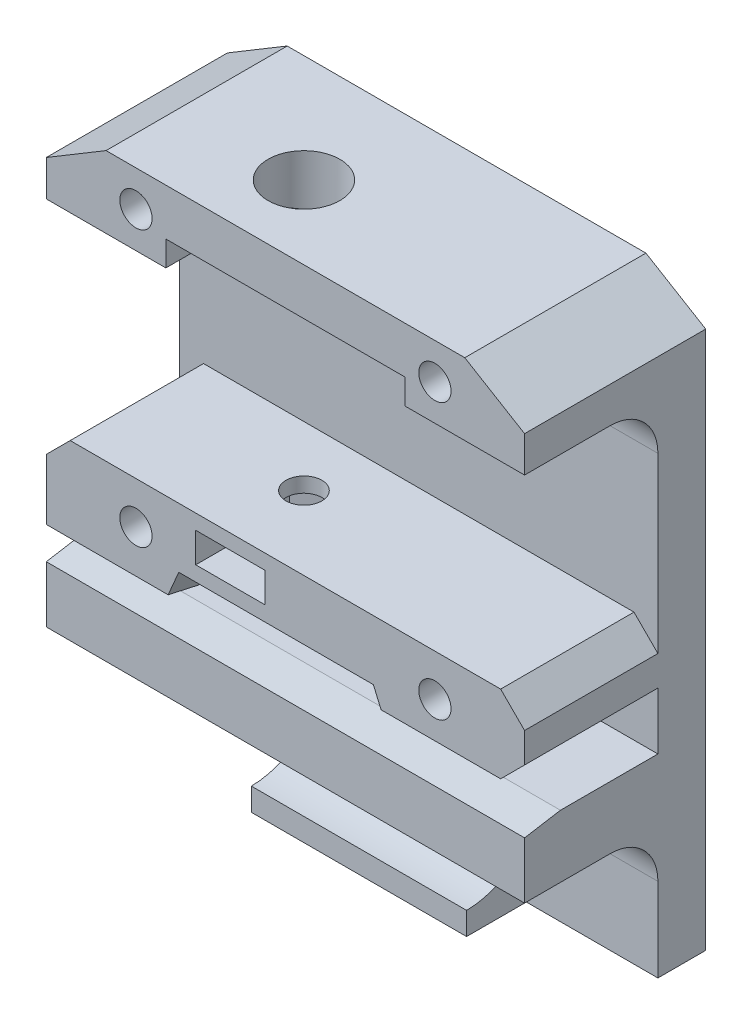
SolidWorks part; units mm, degrees
material "ABS"
ref_plane "Front Plane" through (0, 0, 0) normal (0, 0, 1) x (1, 0, 0)
ref_plane "Top Plane" through (0, 0, 0) normal (0, 1, 0) x (1, 0, 0)
ref_plane "Right Plane" through (0, 0, 0) normal (1, 0, 0) x (0, 0, -1)
sketch "Sketch1" plane through (0, 0, 0) normal (0, 0, 1) x (1, 0, 0)
  line L1 (-23.7591, 22) -> (52.715, 22) construction
  line L2 (0, -10) -> (0, 38)
  line L3 (0, 38) -> (40, 38)
  line L4 (40, -10) -> (40, 38)
  line L6 (0, -10) -> (40, -10)
  point P2 (0, 22)
  point P9 (40, 22)
  point P10 (0, 22)
  point P13 (40, 22)
  dimension "D1" = 48
  dimension "D2" = 40
extrude "Boss-Extrude1" add sketch "Sketch1" along normal blind 4
ref_plane "Plane2" through (0, 13, 0) normal (0, -1, 0) x (1, 0, 0)
sketch "Sketch2" plane through (0, 0, 4) normal (0, 0, 1) x (1, 0, 0)
  line L0 (20, 38) -> (20, 20.7808) construction
  line L1 (15.9, 33) -> (24.1, 33)
  line L2 (15.9, 33) -> (15.9, 23)
  line L3 (15.9, 23) -> (24.1, 23)
  line L4 (24.1, 33) -> (24.1, 23)
  line L5 (40, 38) -> (0, 38) construction
  line L6 (-2.2, 13) -> (2.2, 13) construction
  line L9 (2, 3) -> (10.2, 3)
  line L10 (2, 3) -> (2, -7)
  line L11 (2, -7) -> (10.2, -7)
  line L12 (10.2, 3) -> (10.2, -7)
  line L14 (29.8, 3) -> (29.8, -7)
  line L15 (38, -7) -> (29.8, -7)
  line L16 (38, 3) -> (38, -7)
  line L17 (38, 3) -> (29.8, 3)
  line L18 (15.9, 28) -> (24.1, 28) construction
  line L19 (2, -2) -> (38, -2) construction
  dimension "D1" = 8.2
  dimension "D2" = 10
  dimension "D3" = 20
  dimension "D4" = 4.1
  dimension "D5" = 30
  dimension "D6" = 2
extrude "Cut-Extrude1" [suppressed] cut sketch "Sketch2" against normal blind 1
sketch "Sketch3" [suppressed] plane through (0, 0, 3) normal (0, 0, 1) x (1, 0, 0)
  line L0 (15.9, 33) -> (15.9, 23) construction
  line L1 (15.9, 32.1) -> (24.1, 32.1)
  line L2 (15.9, 32.1) -> (15.9, 23.9)
  line L3 (15.9, 23.9) -> (24.1, 23.9)
  line L4 (24.1, 32.1) -> (24.1, 23.9)
  line L5 (24.1, 23) -> (24.1, 33) construction
  line L6 (24.1, 33) -> (15.9, 33) construction
  line L7 (15.9, 23) -> (24.1, 23) construction
  line L8 (2, 3) -> (2, -7) construction
  line L9 (2, 2.1) -> (10.2, 2.1)
  line L10 (2, 2.1) -> (2, -6.1)
  line L11 (2, -6.1) -> (10.2, -6.1)
  line L12 (10.2, 2.1) -> (10.2, -6.1)
  line L13 (10.2, -7) -> (10.2, 3) construction
  line L14 (29.8, 3) -> (29.8, -7) construction
  line L15 (29.8, 2.1) -> (38, 2.1)
  line L16 (29.8, 2.1) -> (29.8, -6.1)
  line L17 (29.8, -6.1) -> (38, -6.1)
  line L18 (38, 2.1) -> (38, -6.1)
  line L19 (38, -7) -> (38, 3) construction
  line L20 (2, -7) -> (10.2, -7) construction
  dimension "D1" = 0.9
  dimension "D2" = 0.9
  dimension "D3" = 0.9
extrude "Cut-Extrude2" [suppressed] cut sketch "Sketch3" against normal blind 4
chamfer "Chamfer1" [suppressed] distance 1 angle 45
sketch "Sketch4" [suppressed] plane through (0, 0, 3) normal (0, 0, 1) x (1, 0, 0)
  line L0 (24.1, 35.1) -> (15.9, 35.1) construction
  line L1 (15.9, 35.1) -> (15.9, 26.9) construction
  line L2 (2, 1) -> (38, 1) construction
  line L3 (2, 5.1) -> (2, -3.1) construction
  line L4 (38, -7) -> (38, 3) construction
  line L5 (6.1, 2.1) -> (6.1, -3.1) construction
  line L7 (2, -3.1) -> (10.2, -3.1) construction
  line L8 (33.9, 2.1) -> (33.9, -3.1) construction
  line L10 (29.8, -3.1) -> (38, -3.1) construction
  line L12 (10.2, 2.1) -> (2, 2.1) construction
  line L13 (38, 2.1) -> (29.8, 2.1) construction
  circle A0 centre (20, 31) radius 1.65
  circle A1 centre (6.1, 1) radius 1.65
  circle A2 centre (33.9, 1) radius 1.65
  dimension "D1" = 3.3
  dimension "D2" = 4.1
  dimension "D3" = 4.1
extrude "Cut-Extrude3" [suppressed] cut sketch "Sketch4" against normal through all
ref_plane "Plane1" through (20, 0, 0) normal (1, 0, 0) x (0, 0, -1)
sketch "Sketch5" plane through (0, 0, 4) normal (0, 0, 1) x (1, 0, 0)
  line L0 (-5.9966, 13) -> (42.103, 13) construction
  line L1 (0.9, 8.125) -> (0, 8.125)
  line L2 (40, 6.225) -> (40, 1)
  line L3 (0, 6.225) -> (40, 6.225)
  line L4 (40, 15.5) -> (40, 9)
  line L5 (40, 9) -> (28, 9)
  line L6 (20, -2.2) -> (20, 2.2) construction
  line L7 (0, -10) -> (40, -10) construction
  line L8 (0, 1) -> (40, 1)
  line L9 (27.3571, 10.5) -> (11.0812, 10.5)
  line L10 (28, 9) -> (27.3571, 10.5)
  line L11 (5.9219, 8.125) -> (6.2219, 7.425)
  line L12 (11.0812, 10.5) -> (9.7634, 7.425)
  line L13 (6.2219, 7.425) -> (7.2317, 7.425)
  line L14 (-2.2, 13) -> (2.2, 13) construction
  line L15 (7.2317, 7.425) -> (7.5317, 8.125)
  line L16 (8.5004, 8.125) -> (8.8004, 7.425)
  line L17 (8.8004, 7.425) -> (9.7634, 7.425)
  line L18 (5.9219, 8.125) -> (5, 8.125)
  line L23 (1.2, 7.425) -> (0.9, 8.125)
  line L27 (2.5, 8.125) -> (2.2, 7.425)
  line L28 (2.2, 7.425) -> (1.2, 7.425)
  line L29 (11, -10) -> (29, -10)
  line L30 (3.7, 7.425) -> (3.4, 8.125)
  line L31 (3.4, 8.125) -> (2.5, 8.125)
  line L32 (5, 8.125) -> (4.7, 7.425)
  line L33 (4.7, 7.425) -> (3.7, 7.425)
  line L34 (11, -10) -> (11, -5)
  line L36 (8.5004, 8.125) -> (7.5317, 8.125)
  line L40 (40, -10) -> (40, 38) construction
  line L42 (40, 15.5) -> (0, 15.5)
  line L43 (0, 15.5) -> (0, 8.125)
  line L46 (0, 38) -> (0, -10) construction
  line L47 (0, 32) -> (40, 32)
  line L48 (0, 32) -> (0, 38)
  line L49 (11, -5) -> (29, -5)
  line L50 (40, 32) -> (40, 38)
  line L51 (0, 38) -> (40, 38)
  line L52 (29, -10) -> (29, -5)
  line L53 (40, 38) -> (0, 38) construction
  line L62 (0, 6.225) -> (0, 1)
  point P84 (20, 6.225)
  dimension "D2" = 0.7
  dimension "D3" = 0.9
  dimension "D4" = 0.3
  dimension "D5" = 0.3
  dimension "D7" = 1
  dimension "D9" = 5
  dimension "D10" = 4
  dimension "D11" = 1.9
  dimension "D14" = 18
  dimension "D15" = 5
  dimension "D19" = 2.5
  dimension "D8" = 4.875
  dimension "D12" = 12
  dimension "D13" = 12
  dimension "D6" = 19
extrude "Boss-Extrude2" add sketch "Sketch5" along normal blind 11.15 and the other way up to surface (4 mm away) other way up to face at (20, 14, 0)
fillet "Fillet1" radius 4 2 edges at (20, 32, 4) (20, 1, 4) tangent propagation no
sketch "Sketch6" plane through (0, 0, 15.15) normal (0, 0, 1) x (1, 0, 0)
  line L0 (7.5, 41.1026) -> (7.5, 12.7734) construction
  line L2 (20, 38) -> (20, 13.7163) construction
  line L3 (20, -2.2) -> (20, 2.2) construction
  line L4 (-2.2, 13) -> (2.2, 13) construction
  line L6 (40, 38) -> (0, 38) construction
  circle A0 centre (7.5, 35) radius 1.35
  circle A1 centre (7.5, 12) radius 1.35
  circle A2 centre (32.5, 35) radius 1.35
  circle A3 centre (32.5, 12) radius 1.35
  dimension "D1" = 2.7
  dimension "D2" = 23
  dimension "D3" = 22
  dimension "D4" = 12.5
extrude "Cut-Extrude4" cut sketch "Sketch6" against normal through all
chamfer "Chamfer2" distance 2 angle 45 3 edges at (0, 15.5, 9.575) (40, 9, 9.575) (40, 15.5, 9.575)
sketch "Sketch7" plane through (0, 0, 4) normal (0, 0, 1) x (1, 0, 0)
  line L0 (0, 28) -> (0, 13.5) construction
  line L1 (0, 22) -> (40, 22)
  line L2 (0, 22) -> (0, 15.5)
  line L3 (0, 15.5) -> (40, 15.5)
  line L4 (40, 22) -> (40, 15.5)
  line L7 (38, 15.5) -> (2, 15.5) construction
  line L8 (-2.2, 13) -> (2.2, 13) construction
  dimension "D1" = 9
extrude "Cut-Extrude5" [suppressed] cut sketch "Sketch7" against normal blind 3
fillet "Fillet2" [suppressed] radius 3
chamfer "Chamfer3" distance 3 distance2 1 2 edges at (1.7, 7.425, 15.15) (4.2, 7.425, 15.15) first distance on face at (1.7, 7.425, 9.575) first distance on face at (4.2, 7.425, 9.575)
chamfer "Chamfer4" distance 3 distance2 0.5 1 edges at (20, 6.225, 15.15) first distance on face at (20, 6.225, 9.575)
sketch "Sketch8" plane through (20, 0, 0) normal (1, 0, 0) x (0, 0, -1)
  line L0 (-9, 28) -> (-9, -2) construction
  line L1 (-15.15, 38) -> (0, 38) construction
  line L2 (-4, 6.225) -> (-4, 11) construction
  line L4 (-9, 34.1) -> (-18.8209, 34.1)
  line L5 (-18.8209, 34.1) -> (-18.8209, 21.9)
  line L6 (-18.8209, 21.9) -> (-9, 21.9)
  line L8 (-18.8209, -10.4726) -> (-18.8209, -3.1942)
  line L9 (-18.8209, -3.1942) -> (-13.3134, 2.3134)
  line L10 (-9, -8.1) -> (-9, -10.4726)
  line L11 (-9, -10.4726) -> (-18.8209, -10.4726)
  arc A0 (-9, 21.9) -> (-9, 34.1) centre (-9, 28) ccw
  arc A1 (-9, -8.1) -> (-13.3134, 2.3134) centre (-9, -2) ccw
  dimension "D2" = 12.2
  dimension "D1" = 30
  dimension "D3" = 10
  dimension "D4" = 5
  dimension "D5" = 45
extrude "Cut-Extrude6" cut sketch "Sketch8" against normal blind 10 and the other way blind 10
sketch "Sketch12" plane through (0, 38, 0) normal (0, 1, 0) x (1, 0, 0)
  line L1 (10, -4) -> (0, -4) construction
  circle A0 centre (15.4, -9) radius 3
  dimension "D3" = 6
  dimension "D1" = 5
  dimension "D2" = 15.4
extrude "Cut-Extrude8" cut sketch "Sketch12" against normal up to surface (22.5 mm away) up to face at (20, 15.5, 9.575)
sketch "Sketch13" plane through (0, 15.5, 0) normal (0, 1, 0) x (1, 0, 0)
  circle A0 centre (15.4, -9) radius 1.5
  circle A1 centre (15.4, -9) radius 3 construction
  dimension "D1" = 3
extrude "Cut-Extrude10" cut sketch "Sketch13" against normal offset from surface (10.275 mm away) 1 up to face at (20, 6.225, 8.075) offset beyond the face yes
sketch "Sketch9" plane through (0, 13, 0) normal (0, -1, 0) x (1, 0, 0)
  line L0 (12.5, 16.8153) -> (18.3, 16.8153)
  line L1 (15.4, 5.6514) -> (18.3, 7.3257)
  line L2 (18.3, 7.3257) -> (18.3, 16.8153)
  line L5 (12.5, 16.8153) -> (12.5, 7.3257)
  line L6 (12.5, 7.3257) -> (15.4, 5.6514)
  line L8 (13.9872, 11.5329) -> (12.1308, 10.4612) [skipped]
  line L9 (16.8128, 11.5329) -> (14.9564, 12.6047) [skipped]
  circle A0 centre (15.4, 9) radius 2.9 construction
  arc A1 (18.4, 9) -> (12.4, 9) centre (15.4, 9) ccw construction
  dimension "D1" = 5.8
extrude "Cut-Extrude7" cut sketch "Sketch9" against normal blind 1.25 and the other way blind 1.25
chamfer "Chamfer5" distance 5 distance2 3 1 edges at (0, 38, 7.575) first distance on face at (15.4, 38, 12)
chamfer "Chamfer6" distance 3 distance2 5 1 edges at (40, 38, 7.575) first distance on face at (40, 12.696, 8.3172)
sketch "Sketch14" plane through (0, 0, 0) normal (0, 0, -1) x (-1, 0, 0)
  line L1 (0, 35) -> (0, -10) construction
  line L4 (-18, 28.5) -> (-5, 28.5) construction
  line L6 (-35, 38) -> (-5, 38) construction
  circle A4 centre (-5, 28.5) radius 1.35
  circle A5 centre (-18, 28.5) radius 1.35
  dimension "D11" = 5
  dimension "D14" = 2.7
  dimension "D10" = 9.5
  dimension "D12" = 13
extrude "Cut-Extrude11" cut sketch "Sketch14" against normal blind 10
